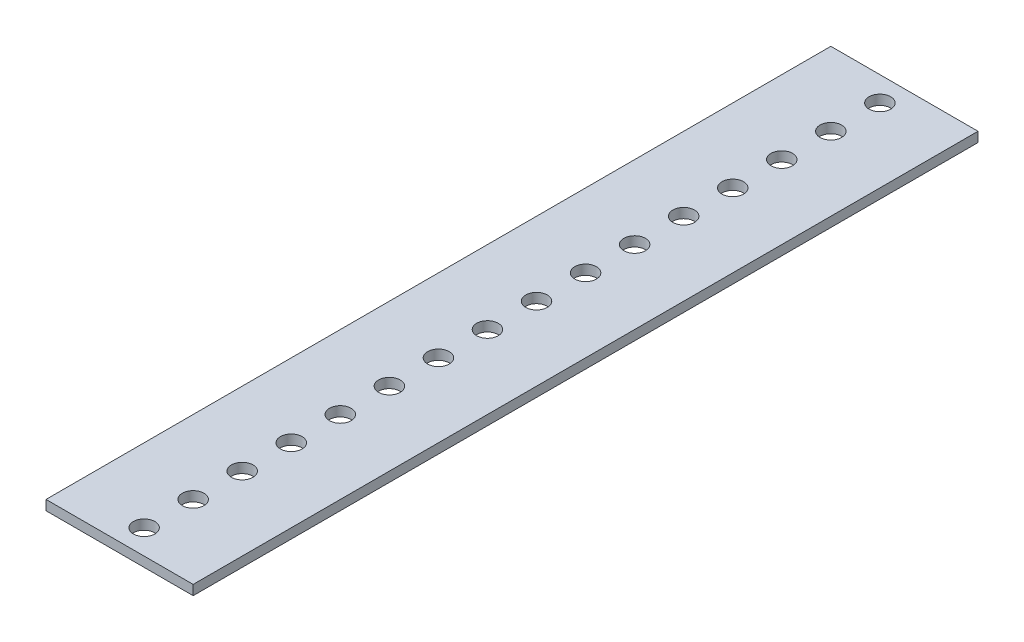
SolidWorks part; units mm, degrees
ref_plane "Front Plane" through (0, 0, 0) normal (0, 0, 1) x (1, 0, 0)
ref_plane "Top Plane" through (0, 0, 0) normal (0, 1, 0) x (1, 0, 0)
ref_plane "Right Plane" through (0, 0, 0) normal (1, 0, 0) x (0, 0, -1)
sketch "Sketch2" plane through (0, 0, 0) normal (0, 1, 0) x (1, 0, 0)
  line L1 (-19.05, -101.6) -> (19.05, -101.6)
  line L2 (-19.05, -101.6) -> (-19.05, 101.6)
  line L3 (-19.05, 101.6) -> (19.05, 101.6)
  line L4 (19.05, -101.6) -> (19.05, 101.6)
  line L5 (-19.05, -101.6) -> (19.05, 101.6) construction
  line L6 (-19.05, 101.6) -> (19.05, -101.6) construction
  point P0 (0, 0)
  dimension "D1" = 38.1
  dimension "D2" = 203.2
extrude "Boss-Extrude1" add sketch "Sketch2" along normal blind 2.54
sketch "Sketch3" plane through (0, 2.54, 0) normal (0, 1, 0) x (1, 0, 0)
  circle A0 centre (0, -95.25) radius 2.794
extrude "Cut-Extrude1" cut sketch "Sketch3" against normal blind 2.54
pattern_linear "LPattern1" count 16 spacing 12.7 along (0, 0, -1) of "Cut-Extrude1"
